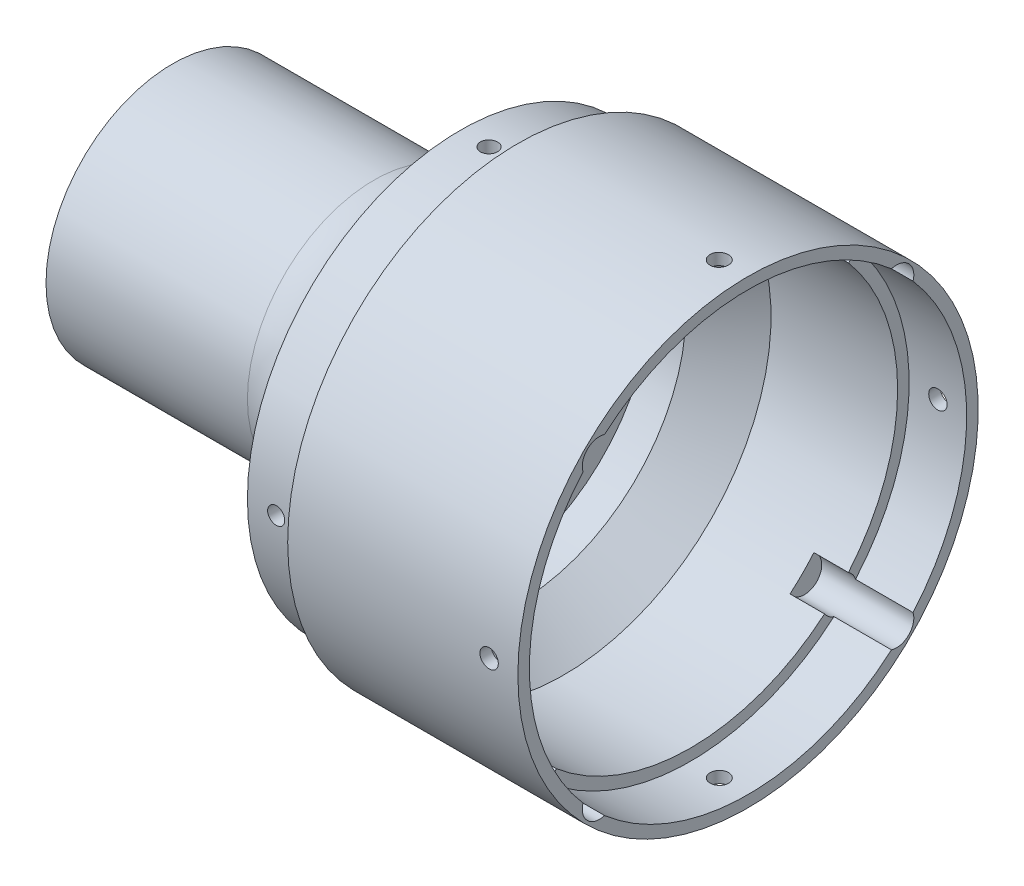
SolidWorks part; units mm, degrees
ref_plane "Ön Düzlem" through (0, 0, 0) normal (0, 0, 1) x (1, 0, 0)
ref_plane "Üst Düzlem" through (0, 0, 0) normal (0, 1, 0) x (1, 0, 0)
ref_plane "Sağ Düzlem" through (0, 0, 0) normal (1, 0, 0) x (0, 0, -1)
ref_axis "Eksen1" through (-88.99, 0, 0) along (1, 0, 0)
sketch "Çizim1" plane through (0, 0, 0) normal (0, 0, 1) x (1, 0, 0)
  line L2 (-60, 40) -> (-60, 37)
  line L3 (-60, 37) -> (-70, 37)
  line L4 (-70, 37) -> (-70, 22)
  line L14 (-20, 40) -> (-60, 40)
  line L49 (-66, 18.2) -> (-66, 29.2)
  line L52 (-66, 18.2) -> (-118, 18.2)
  line L53 (-118, 18.2) -> (-118, 4)
  line L54 (-118, 4) -> (-120, 4)
  line L55 (-120, 4) -> (-120, 22)
  line L56 (-120, 22) -> (-70, 22)
  line L57 (-20, 40) -> (-20, 38)
  line L58 (-20, 38) -> (-30, 38)
  line L60 (-30, 38) -> (-30, 36)
  line L63 (-60, 29.2) -> (-66, 29.2)
  line L64 (-30, 36) -> (-52, 36)
  line L65 (-52, 36) -> (-60, 29.2)
revolve "Döndür1" add sketch "Çizim1" angle 360 about axis through (-88.99, 0, 0) along (1, 0, 0)
sketch "Çizim12" plane through (0, 0, 0) normal (1, 0, 0) x (0, 0, -1)
  circle A0 centre (12.5, 0) radius 1.6
extrude "Kes-Ekstrüzyon1" cut sketch "Çizim12" against normal through all
pattern_circular "Dairesel Kaplama1" count 6 over 360 about axis through (-88.99, 0, 0) along (1, 0, 0) of "Kes-Ekstrüzyon1"
sketch "Çizim13" plane through (0, 0, 0) normal (0, 0, 1) x (1, 0, 0)
  line L2 (-88.99, 0) -> (88.99, 0) construction
  circle A0 centre (-65, 0) radius 1.49
extrude "Kes-Ekstrüzyon2" cut sketch "Çizim13" along normal blind 5 from offset 32
pattern_circular "Dairesel Kaplama2" count 4 over 360 about axis through (-88.99, 0, 0) along (1, 0, 0) of "Kes-Ekstrüzyon2"
sketch "Çizim14" plane through (0, 0, 0) normal (0, 0, 1) x (1, 0, 0)
  line L2 (-88.99, 0) -> (88.99, 0) construction
  circle A0 centre (-25, 0) radius 1.6
extrude "Kes-Ekstrüzyon3" cut sketch "Çizim14" against normal through all contours A0
pattern_circular "Dairesel Kaplama3" count 4 over 360 about axis through (-88.99, 0, 0) along (1, 0, 0) of "Kes-Ekstrüzyon3"
sketch "Çizim15" plane through (0, 0, 0) normal (1, 0, 0) x (0, 0, -1)
  circle A1 centre (25.8094, 25.8094) radius 3
extrude "Kes-Ekstrüzyon5" cut sketch "Çizim15" against normal blind 36
pattern_circular "Dairesel Kaplama4" count 4 over 360 about axis through (-88.99, 0, 0) along (1, 0, 0) of "Kes-Ekstrüzyon5"
fillet "Radyus1" radius 15 1 edges at (-70, 0, 22)
